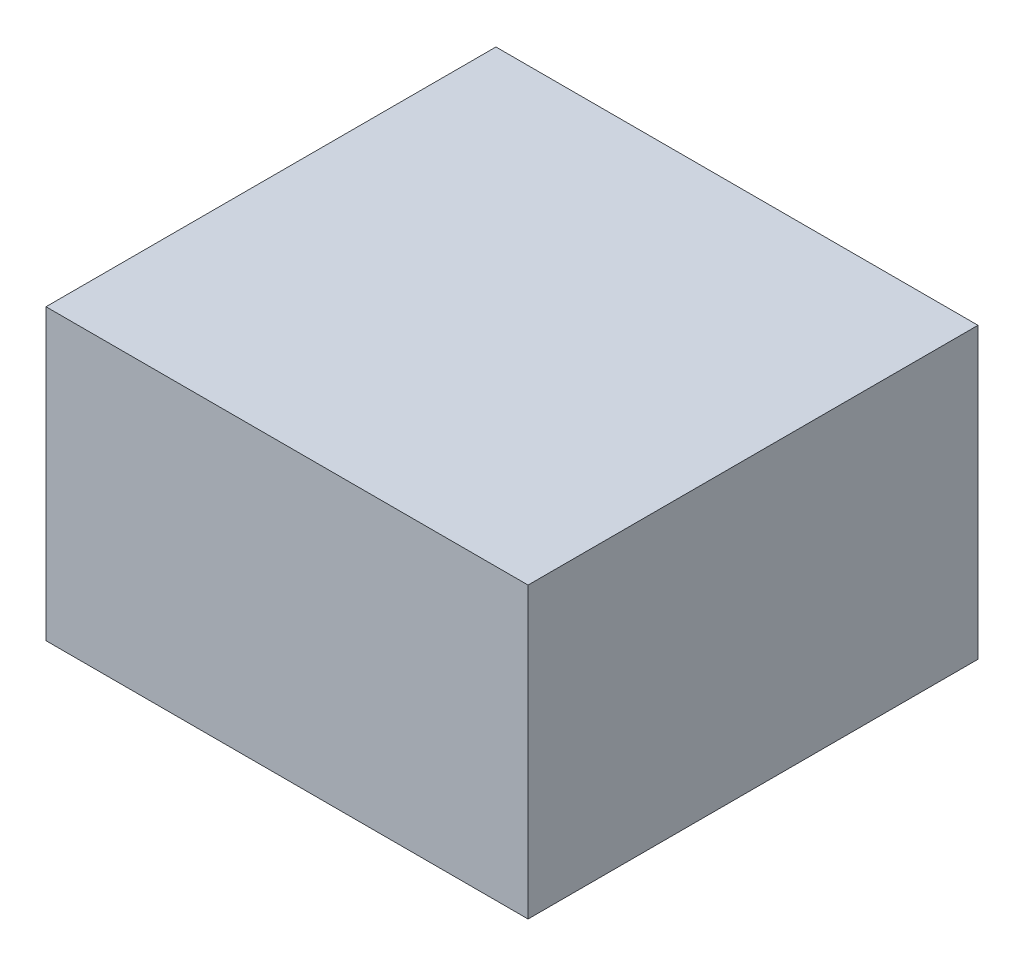
SolidWorks part; units mm, degrees
ref_plane "Front Plane" through (0, 0, 0) normal (0, 0, 1) x (1, 0, 0)
ref_plane "Top Plane" through (0, 0, 0) normal (0, 1, 0) x (1, 0, 0)
ref_plane "Right Plane" through (0, 0, 0) normal (1, 0, 0) x (0, 0, -1)
sketch "Sketch1" plane through (0, 0, 0) normal (0, 1, 0) x (1, 0, 0)
  line L1 (-75, 70) -> (75, 70)
  line L2 (-75, 70) -> (-75, -70)
  line L3 (-75, -70) -> (75, -70)
  line L4 (75, 70) -> (75, -70)
  line L5 (-75, 70) -> (75, -70) construction
  line L6 (-75, -70) -> (75, 70) construction
  point P0 (0, 0)
  dimension "D1" = 140
  dimension "D2" = 150
extrude "Boss-Extrude1" add sketch "Sketch1" along normal blind 90
